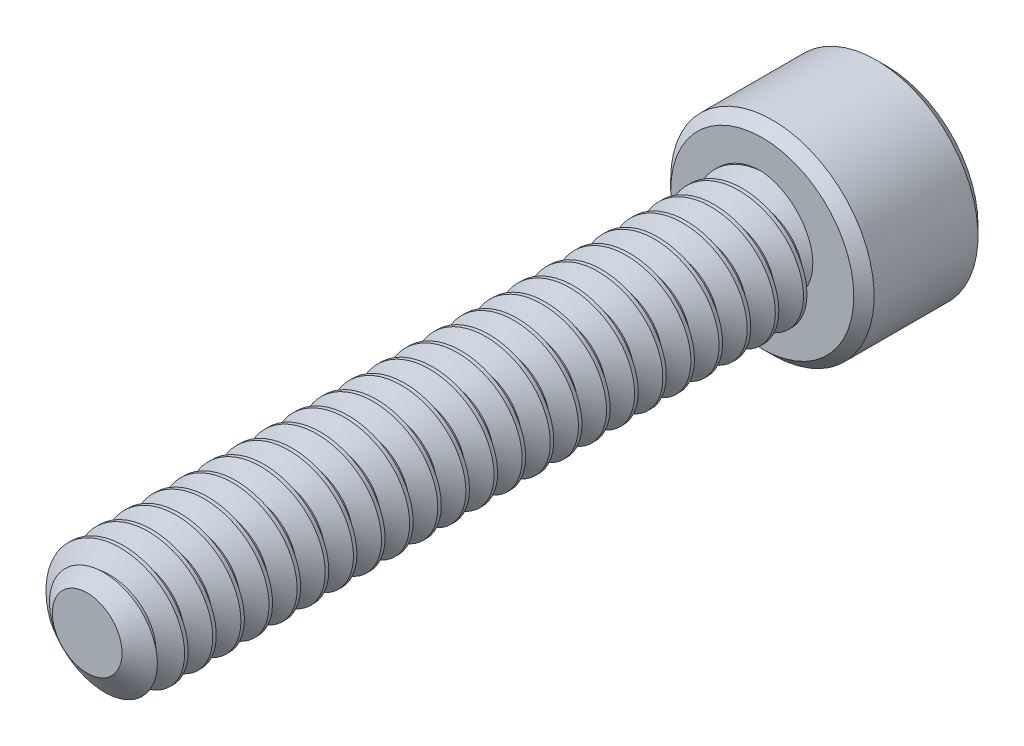
SolidWorks part; units mm, degrees
ref_plane "Front Plane" through (0, 0, 0) normal (0, 0, 1) x (1, 0, 0)
ref_plane "Top Plane" through (0, 0, 0) normal (0, 1, 0) x (1, 0, 0)
ref_plane "Right Plane" through (0, 0, 0) normal (1, 0, 0) x (0, 0, -1)
sketch "Sketch1" plane through (0, 0, 0) normal (0, 0, 1) x (1, 0, 0)
  circle A0 centre (0, 0) radius 1.7526
  dimension "OD" = 3.5052
extrude "Extrude1" add sketch "Sketch1" against normal blind 19.05
sketch "Sketch2" plane through (0, 0, 0) normal (0, 0, 1) x (1, 0, 0)
  circle A0 centre (0, 0) radius 1.7526 construction
  circle A1 centre (0, 0) radius 1.7526
curve "Helix/Spiral1" pitch 0.7937 height 19.8438 turns 25 parameters "pitch"=0.7937
sketch "Sketch3" plane through (0, 0, 0) normal (1, 0, 0) x (0, 0, -1)
  line L0 (-0.6945, 1.7526) -> (-0.3969, 1.237)
  line L1 (-0.3969, 1.237) -> (-0.2977, 1.237)
  line L2 (-0.2977, 1.237) -> (0, 1.7526)
  line L3 (-0.6945, 1.7526) -> (0, 1.7526)
  line L4 (-0.3473, 1.7526) -> (-0.3473, 1.237) construction
  line L5 (-0.5457, 1.4948) -> (-0.1488, 1.4948) construction
  line L6 (0, 1.7526) -> (0, -1.7526) construction
  dimension "D1" = 0.0992
  dimension "D2" = 0.3969
  dimension "D3" = 60
sweep "Cut-Sweep1" cut profiles "Sketch3" path "Helix/Spiral1"
sketch "Sketch4" plane through (0, 0, 0) normal (1, 0, 0) x (0, 0, -1)
  line L0 (0.5388, 1.7526) -> (0, 0.983)
  line L1 (0, 0.983) -> (0, 1.7526)
  line L2 (0.5388, 1.7526) -> (0, 1.7526)
  line L3 (-0.6945, 1.7526) -> (0, 1.7526) construction
  line L4 (0, 0) -> (7.0209, 0) construction
  dimension "D1" = 55
  dimension "D2" = 0.254
revolve "Cut-Revolve1" cut sketch "Sketch4" angle 360 about L4
sketch "Sketch5" plane through (0, 0, 0) normal (1, 0, 0) x (0, 0, -1)
  line L0 (19.05, -1.2539) -> (19.05, 1.2505) construction
  line L1 (19.05, 1.8796) -> (87.4327, 1.8796)
  line L2 (19.05, 1.8796) -> (19.05, 0)
  line L3 (19.05, 0) -> (87.3125, 0)
  line L4 (87.3125, 1.5494) -> (87.3125, 0)
  line L5 (87.4327, 1.8796) -> (87.3125, 1.5494)
  line L6 (0, 0) -> (9.9695, 0) construction
  point P3 (87.3125, 1.8796)
  point P10 (87.3125, 1.8796)
  dimension "D1" = 0.3302
  dimension "Thread min" = 87.3125
  dimension "D2" = 0.127
  dimension "D3" = 20
revolve "partially thread" [suppressed] add sketch "Sketch5" angle 360 about L6
sketch "Sketch6" plane through (0, 0, -19.05) normal (0, 0, -1) x (-1, 0, 0)
  circle A0 centre (0, 0) radius 2.8702
  dimension "head dia" = 5.7404
extrude "Extrude2" add sketch "Sketch6" along normal blind 3.5052
sketch "Sketch7" plane through (0, 0, -22.5552) normal (0, 0, -1) x (-1, 0, 0)
  line L1 (0, 1.604) -> (-1.3891, 0.802)
  line L2 (-1.3891, 0.802) -> (-1.3891, -0.802)
  line L3 (-1.3891, -0.802) -> (0, -1.604)
  line L4 (0, -1.604) -> (1.3891, -0.802)
  line L5 (1.3891, -0.802) -> (1.3891, 0.802)
  line L6 (1.3891, 0.802) -> (0, 1.604)
  circle A0 centre (0, 0) radius 1.3891 construction
  dimension "hex dia" = 2.7781
extrude "Cut-Extrude1" cut sketch "Sketch7" against normal blind 2.0836
sketch "Sketch8" plane through (0, 0, -22.5552) normal (0, 0, -1) x (-1, 0, 0)
  circle A0 centre (0, 0) radius 1.604
extrude "Cut-Extrude2" cut sketch "Sketch8" against normal through all draft 45
chamfer "Chamfer1" distance 0.287 angle 45 2 edges at (-2.8702, 0, -22.5552) (-2.8702, 0, -19.05)
sketch "Sketch9" plane through (0, 0, 0) normal (1, 0, 0) x (0, 0, -1)
  line L0 (0, 1.7526) -> (0, -1.7526) construction
  line L1 (4.3656, 1.7526) -> (4.3656, -1.7526) construction
  dimension "D1" = 4.3656
equation "\"D3@Helix/Spiral1\" = \"screw length@Extrude1\"+\"pitch@Helix/Spiral1\""
equation "\"D1@Sketch3\" = \"pitch@Helix/Spiral1\"*.125"
equation "\"D2@Sketch3\" = \"pitch@Helix/Spiral1\"*.5"
equation "\"D1@Cut-Extrude1\" = \"hex dia@Sketch7\"*.75"
equation "\"D1@Chamfer1\" = \"head dia@Sketch6\"*.05"
equation "\"D1@Sketch9\" = \"pitch@Helix/Spiral1\"*5.5"
